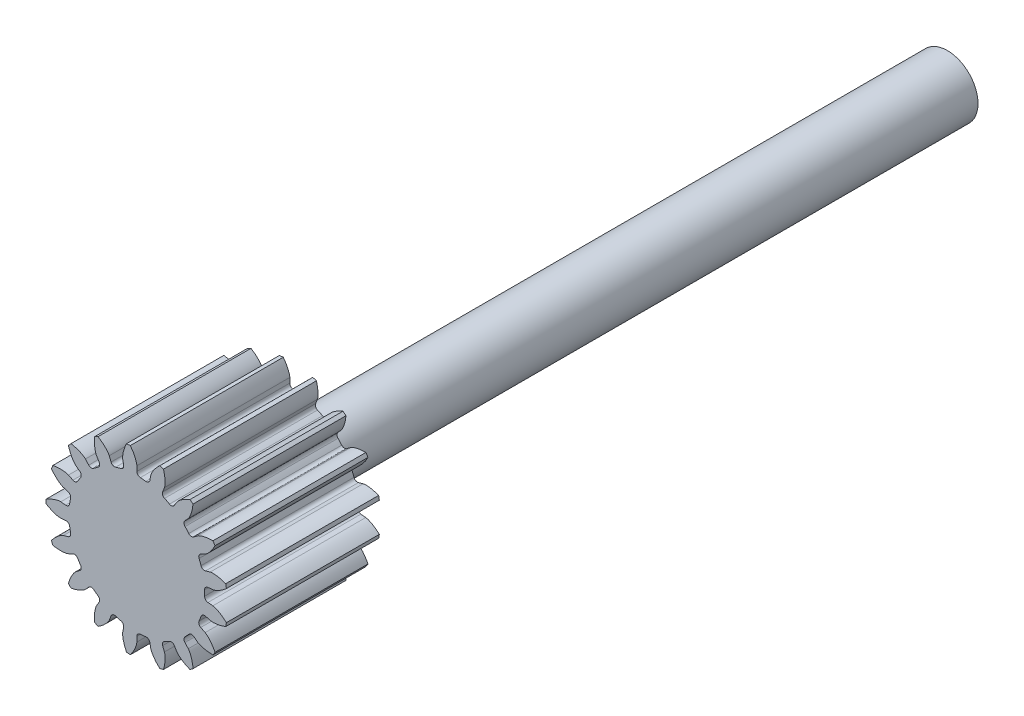
SolidWorks part; units mm, degrees
ref_plane "Front Plane" through (0, 0, 0) normal (0, 0, 1) x (1, 0, 0)
ref_plane "Top Plane" through (0, 0, 0) normal (0, 1, 0) x (1, 0, 0)
ref_plane "Right Plane" through (0, 0, 0) normal (1, 0, 0) x (0, 0, -1)
ref_axis "Gear Axis" through (0, 0, -91.3) along (0, 0, 1)
sketch "Blank Sketch" plane through (0, 0, 0) normal (0, 0, 1) x (1, 0, 0)
  circle A0 centre (0, 0) radius 11.875
  dimension "OD" = 23.75
extrude "Blank" add sketch "Blank Sketch" along normal blind 20
sketch "Tooth Space Sketch" plane through (0, 0, 0) normal (0, 0, 1) x (1, 0, 0)
  line L0 (9.9424, 0.9134) -> (9.2988, 0.8543)
  line L1 (9.9424, -0.9134) -> (9.2988, -0.8543)
  line L2 (12.7535, 3.1007) -> (12.7535, -3.1007)
  arc A0 (9.2988, 0.8543) -> (8.8676, 0.3619) centre (9.3422, 0.3813) ccw
  arc A1 (8.8676, -0.3619) -> (9.2988, -0.8543) centre (9.3422, -0.3813) ccw
  arc A2 (8.8676, -0.3619) -> (8.8676, 0.3619) centre (0, 0) ccw
  spline S0 degree 4 poles (9.9424, 0.9134) (9.9477, 0.914) (9.9627, 0.9159) (9.9908, 0.9208) (10.0364, 0.9304) (10.094, 0.9451) (10.1679, 0.9668) (10.254, 0.9959) (10.3477, 1.0316) (10.4483, 1.0743) (10.5475, 1.1204) (10.6453, 1.1696) (10.7417, 1.2214) (10.857, 1.2875) (10.9932, 1.3713) (11.1493, 1.4758) (11.3226, 1.602) (11.4947, 1.7386) (11.6604, 1.8795) (11.8233, 2.0291) (11.9776, 2.179) (12.1329, 2.3418) (12.2737, 2.4958) (12.4257, 2.676) (12.5467, 2.8236) (12.6999, 3.0262) (12.7884, 3.1482) (12.8897, 3.2936) (12.9335, 3.3596) (12.9605, 3.4002) knots 0 0 0 0 0 0.005377 0.015084 0.028532 0.04661 0.064855 0.092111 0.119476 0.146842 0.174209 0.201575 0.228941 0.256307 0.307035 0.361767 0.4165 0.471232 0.525964 0.580697 0.635429 0.690161 0.744894 0.799626 0.854358 0.909091 0.954545 1 1 1 1 1 construction
  spline S1 degree 4 poles (9.9424, 0.9134) (9.9477, 0.914) (9.9627, 0.9159) (9.9908, 0.9208) (10.0364, 0.9304) (10.094, 0.9451) (10.1679, 0.9668) (10.254, 0.9959) (10.3477, 1.0316) (10.4483, 1.0743) (10.5475, 1.1204) (10.6453, 1.1696) (10.7417, 1.2214) (10.857, 1.2875) (10.9932, 1.3713) (11.1493, 1.4758) (11.3226, 1.602) (11.4947, 1.7386) (11.6604, 1.8795) (11.8233, 2.0291) (11.9776, 2.179) (12.1329, 2.3418) (12.2737, 2.4958) (12.4257, 2.676) (12.5467, 2.8236) (12.6667, 2.9823) (12.7243, 3.0604) (12.7535, 3.1007) knots 0 0 0 0 0 0.005377 0.015084 0.028532 0.04661 0.064855 0.092111 0.119476 0.146842 0.174209 0.201575 0.228941 0.256307 0.307035 0.361767 0.4165 0.471232 0.525964 0.580697 0.635429 0.690161 0.744894 0.799626 0.854358 0.909091 0.909091 0.909091 0.909091 0.909091
  spline S2 degree 4 poles (9.9424, -0.9134) (9.9477, -0.914) (9.9627, -0.9159) (9.9908, -0.9208) (10.0364, -0.9304) (10.094, -0.9451) (10.1679, -0.9668) (10.254, -0.9959) (10.3477, -1.0316) (10.4483, -1.0743) (10.5475, -1.1204) (10.6453, -1.1696) (10.7417, -1.2214) (10.857, -1.2875) (10.9932, -1.3713) (11.1493, -1.4758) (11.3226, -1.602) (11.4947, -1.7386) (11.6604, -1.8795) (11.8233, -2.0291) (11.9776, -2.179) (12.1329, -2.3418) (12.2737, -2.4958) (12.4257, -2.676) (12.5467, -2.8236) (12.6999, -3.0262) (12.7884, -3.1482) (12.8897, -3.2936) (12.9335, -3.3596) (12.9605, -3.4002) knots 0 0 0 0 0 0.005377 0.015084 0.028532 0.04661 0.064855 0.092111 0.119476 0.146842 0.174209 0.201575 0.228941 0.256307 0.307035 0.361767 0.4165 0.471232 0.525964 0.580697 0.635429 0.690161 0.744894 0.799626 0.854358 0.909091 0.954545 1 1 1 1 1 construction
  spline S3 degree 4 poles (9.9424, -0.9134) (9.9477, -0.914) (9.9627, -0.9159) (9.9908, -0.9208) (10.0364, -0.9304) (10.094, -0.9451) (10.1679, -0.9668) (10.254, -0.9959) (10.3477, -1.0316) (10.4483, -1.0743) (10.5475, -1.1204) (10.6453, -1.1696) (10.7417, -1.2214) (10.857, -1.2875) (10.9932, -1.3713) (11.1493, -1.4758) (11.3226, -1.602) (11.4947, -1.7386) (11.6604, -1.8795) (11.8233, -2.0291) (11.9776, -2.179) (12.1329, -2.3418) (12.2737, -2.4958) (12.4257, -2.676) (12.5467, -2.8236) (12.6667, -2.9823) (12.7243, -3.0604) (12.7535, -3.1007) knots 0 0 0 0 0 0.005377 0.015084 0.028532 0.04661 0.064855 0.092111 0.119476 0.146842 0.174209 0.201575 0.228941 0.256307 0.307035 0.361767 0.4165 0.471232 0.525964 0.580697 0.635429 0.690161 0.744894 0.799626 0.854358 0.909091 0.909091 0.909091 0.909091 0.909091
  dimension "Root" = 8.875
  dimension "Fillet" = 0.475
extrude "Tooth Space" cut sketch "Tooth Space Sketch" against normal through all both and the other way through all both
pattern_circular "Teeth" count 17 over 360 about axis through (0, 0, -91.3) along (0, 0, 1) of "Tooth Space"
sketch "Bore Sketch" plane through (0, 0, 0) normal (0, 0, 1) x (1, 0, 0)
  circle A0 centre (0, 0) radius 4
  dimension "Bore" = 8
extrude "Bore" cut sketch "Bore Sketch" against normal through all both and the other way through all both
sketch "Sketch1" plane through (0, 0, 20) normal (0, 0, 1) x (1, 0, 0)
  circle A0 centre (0, 0) radius 4 construction
  circle A1 centre (0, 0) radius 4
extrude "Boss-Extrude1" add sketch "Sketch1" against normal blind 106
equation "\"No. of Teeth\"= 17"
equation "\"Module\"= 1.25"
equation "\"Bore Diameter\"= 8"
equation "\"Pressure Angle\"= 20"
equation "\"Outer Diameter\"= ( \"No. of Teeth\" + 2 ) * \"Module\""
equation "\"Pitch Diameter\"= \"No. of Teeth\" * \"Module\""
equation "\"Backlash\" = IIF ( \"Module\" <= 1 , 0.3 * \"Module\" , 0.3 )"
equation "\"Arc Length\"= ( ( \"Module\" * pi ) / 2 + \"Backlash\" )"
equation "\"Fillet Radius\"= 0.38 * \"Module\""
equation "\"Tooth Depth\"= IIF ( \"Module\" <= 1.25 , \"Module\" * 2.4 , \"Module\" * 2.25 )"
equation "\"Face Width\"= 20"
equation "\"Root Diameter\"= \"Outer Diameter\" - 2 * \"Tooth Depth\""
equation "\"Base Diameter\"= \"Pitch Diameter\" * cos ( \"Pressure Angle\" )"
equation "\"Base Radius\"= \"Base Diameter\" / 2"
equation "\"Tooth Thickness\"= \"Module\" * pi - \"Arc Length\""
equation "\"Half Space Angle\"= ( \"Arc Length\" / \"Pitch Diameter\" ) * 180 / pi"
equation "\"Involute Fn\"= tan ( \"Pressure Angle\" ) - \"Pressure Angle\" * pi / 180"
equation "\"Flank Offset\"= \"Arc Length\" / \"Pitch Diameter\" - \"Involute Fn\""
equation "\"Tip Cap Diameter\"= \"Outer Diameter\" + 2 * \"Module\""
equation "\"Flank Start Diameter\"= IIF ( \"Base Diameter\" >= ( \"Root Diameter\" + 3 * \"Fillet Radius\" ) , \"Base Diameter\" , \"Root Diameter\" + 3 * \"Fillet Radius\" )"
equation "\"Involute t1\"= ( abs ( ( \"Flank Start Diameter\" / \"Base Diameter\" ) ^ 2 - 1 ) ) ^ 0.5"
equation "\"Involute t2\"= ( abs ( ( \"Tip Cap Diameter\" / \"Base Diameter\" ) ^ 2 - 1 ) ) ^ 0.5"
equation "\"Flank Arc Radius\"= ( \"Pitch Diameter\" / 2 ) * sin ( \"Pressure Angle\" )"
equation "\"Flank Centre Angle\"= \"Half Space Angle\" + \"Pressure Angle\""
equation "\"OD@Blank Sketch\"= \"Outer Diameter\""
equation "\"Width@Blank\"= \"Face Width\""
equation "\"Root@Tooth Space Sketch\"= \"Root Diameter\" / 2"
equation "\"Fillet@Tooth Space Sketch\"= \"Fillet Radius\""
equation "\"Count@Teeth\"= \"No. of Teeth\""
equation "\"Bore@Bore Sketch\"= \"Bore Diameter\""
